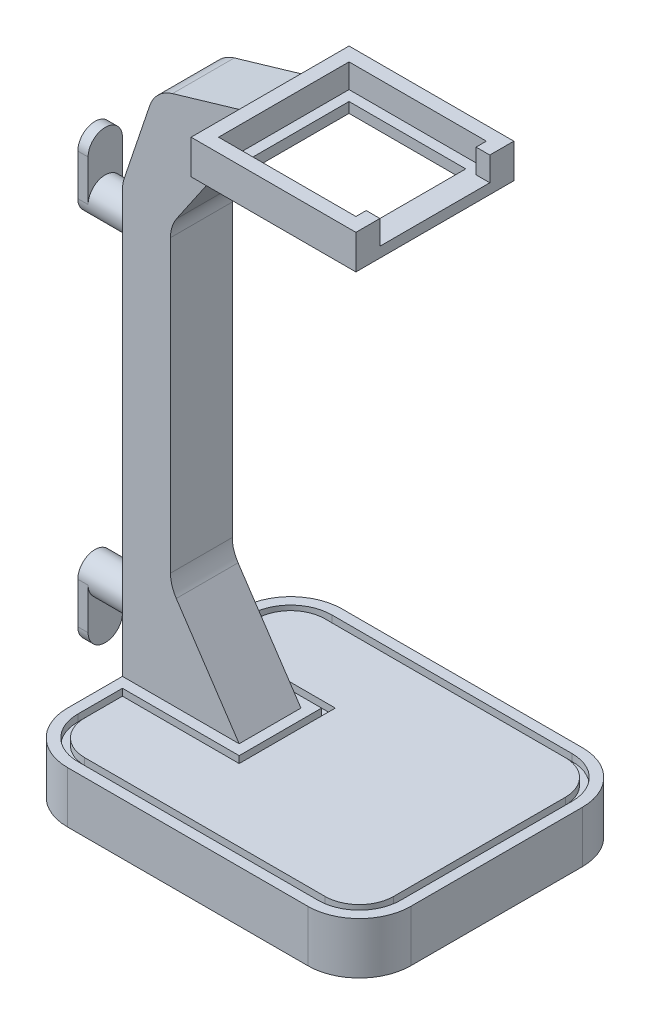
SolidWorks part; units mm, degrees
ref_plane "Front Plane" through (0, 0, 0) normal (0, 0, 1) x (1, 0, 0)
ref_plane "Top Plane" through (0, 0, 0) normal (0, 1, 0) x (1, 0, 0)
ref_plane "Right Plane" through (0, 0, 0) normal (1, 0, 0) x (0, 0, -1)
sketch "Sketch1" plane through (0, 0, 0) normal (0, 1, 0) x (1, 0, 0)
  line L1 (35, -40) -> (-35, -40)
  line L2 (50, -25) -> (50, 25)
  line L3 (35, 40) -> (-35, 40)
  line L4 (-50, -25) -> (-50, 25)
  line L5 (50, -40) -> (-50, 40) construction
  line L6 (50, 40) -> (-50, -40) construction
  arc A0 (50, 25) -> (35, 40) centre (35, 25) ccw
  arc A1 (50, -25) -> (35, -40) centre (35, -25) cw
  arc A2 (-50, -25) -> (-35, -40) centre (-35, -25) ccw
  arc A3 (-50, 25) -> (-35, 40) centre (-35, 25) cw
  point P0 (0, 0)
  dimension "D3" = 15
  dimension "D1" = 100
  dimension "D2" = 80
extrude "Boss-Extrude1" add sketch "Sketch1" along normal blind 15
sketch "Sketch3" plane through (0, 15, 0) normal (0, 1, 0) x (1, 0, 0)
  line L1 (-50, -9) -> (-36, -9)
  line L2 (-50, -9) -> (-50, 9)
  line L3 (-50, 9) -> (-36, 9)
  line L4 (-36, -9) -> (-36, 9)
  line L5 (-50, -9) -> (-36, 9) construction
  line L6 (-50, 9) -> (-36, -9) construction
  line L7 (-50, 25) -> (-50, -25) construction
  line L9 (-35, -40) -> (35, -40) construction
  point P0 (-43, 0)
  dimension "D1" = 14
  dimension "D2" = 18
  dimension "D3" = 40
extrude "Boss-Extrude2" add sketch "Sketch3" along normal blind 150 contours L3 L4 L1 L2
sketch "Sketch5" plane through (0, 0, 9) normal (0, 0, 1) x (1, 0, 0)
  line L0 (-36, 15) -> (-36, 45)
  line L1 (-36, 165) -> (-36, 15) construction
  line L2 (-36, 45) -> (-16, 15)
  line L3 (-35, 15) -> (35, 15) construction
  line L4 (-16, 15) -> (-36, 15)
  dimension "D1" = 30
  dimension "D2" = 20
extrude "Boss-Extrude3" add sketch "Sketch5" against normal blind 18 contours L2 L4 L0
ref_plane "Plane1" through (0, 175, 0) normal (0, 1, 0) x (1, 0, 0)
sketch "Sketch7" plane through (0, 175, 0) normal (0, 1, 0) x (1, 0, 0)
  line L0 (-36, -9) -> (-36, 9) construction
  line L1 (32, -23) -> (-16, -23)
  line L2 (32, -23) -> (32, 23)
  line L3 (32, 23) -> (-16, 23)
  line L4 (-16, -23) -> (-16, 23)
  line L5 (32, -23) -> (-16, 23) construction
  line L6 (32, 23) -> (-16, -23) construction
  line L7 (28, -19) -> (-12, -19)
  line L8 (28, -19) -> (28, 19)
  line L9 (28, 19) -> (-12, 19)
  line L10 (-12, -19) -> (-12, 19)
  line L11 (28, -19) -> (-12, 19) construction
  line L12 (28, 19) -> (-12, -19) construction
  line L13 (50, -25) -> (50, 25) construction
  point P0 (8, 0)
  point P6 (8, 0)
  dimension "D1" = 40
  dimension "D2" = 38
  dimension "D3" = 48
  dimension "D4" = 46
  dimension "D5" = 44
  dimension "D6" = 42
extrude "Boss-Extrude4" add sketch "Sketch7" against normal blind 10 separate body
sketch "Sketch8" plane through (0, 0, 9) normal (0, 0, 1) x (1, 0, 0)
  line L0 (-50, 165) -> (-16, 175)
  line L1 (-16, 175) -> (-16, 165)
  line L2 (-16, 165) -> (-36, 135.7425)
  line L3 (-36, 165) -> (-36, 45) construction
  line L4 (-50, 165) -> (-36, 165)
  line L5 (-36, 165) -> (-36, 135.7425)
extrude "Boss-Extrude5" add sketch "Sketch8" against normal blind 18 contours L0 L1 L2 L5 L4
sketch "Sketch9" plane through (-50, 0, 0) normal (-1, 0, 0) x (0, 0, 1)
  line L0 (-9, 15) -> (9, 15)
split line "Split Line3"
fillet "Fillet2" radius 10 2 edges at (-16, 165, 0) (-36, 135.7425, 0)
chamfer "Chamfer2" distance 10 angle 55 1 edges at (-50, 165, 0)
fillet "Fillet3" radius 10 2 edges at (-50, 139.3319, 0) (-40.4063, 167.8217, 0)
fillet "Fillet4" radius 10 1 edges at (-36, 45, 0)
sketch "Sketch11" plane through (0, 165, 0) normal (0, -1, 0) x (1, 0, 0)
  line L0 (28, 19) -> (28, -19) construction
  line L1 (-12, -19) -> (28, -19)
  line L2 (-12, -19) -> (-12, 19)
  line L3 (-12, 19) -> (28, 19)
  line L4 (28, -19) -> (28, 19)
  line L5 (-12, 19) -> (28, 19) construction
  line L6 (-9, -16) -> (25, -16)
  line L7 (25, -16) -> (25, 16)
  line L8 (-9, 16) -> (25, 16)
  line L9 (-9, -16) -> (-9, 16)
  dimension "D1" = 3
extrude "Boss-Extrude6" add sketch "Sketch11" against normal blind 3
sketch "Sketch12" plane through (32, 0, 0) normal (1, 0, 0) x (0, 0, -1)
  line L0 (-23, 175) -> (23, 175) construction
  line L1 (-16, 175) -> (16, 175)
  line L2 (-16, 175) -> (-16, 165)
  line L3 (-16, 165) -> (16, 165)
  line L4 (16, 175) -> (16, 165)
  line L5 (-23, 165) -> (23, 165) construction
  line L6 (-16, 168) -> (16, 168)
  point P8 (0, 165)
  line M6 (23, 175) -> (-23, 175)
  dimension "D1" = 3
  dimension "D2" = 32
extrude "Cut-Extrude2" cut sketch "Sketch12" against normal blind 5 contours L2 L6 L4 M6
sketch "Sketch13" plane through (0, 15, 0) normal (0, 1, 0) x (1, 0, 0)
  line L16 (-47, 12) -> (-13, 12)
  line L17 (-13, 12) -> (-13, -12)
  line L18 (-13, -12) -> (-47, -12)
  line L19 (-47, -12) -> (-47, -25)
  line L20 (-35, -37) -> (35, -37)
  line L21 (47, -25) -> (47, 25)
  line L22 (35, 37) -> (-35, 37)
  line L24 (-47, 12) -> (-13, 12)
  line L25 (-13, 12) -> (-13, -12)
  line L26 (-13, -12) -> (-47, -12)
  line L28 (-35, -37) -> (35, -37)
  line L29 (47, -25) -> (47, 25)
  line L30 (35, 37) -> (-35, 37)
  line L40 (-45, 14) -> (-11, 14)
  line L41 (-11, 14) -> (-11, -14)
  line L42 (-11, -14) -> (-45, -14)
  line L43 (-45, -14) -> (-45, -25)
  line L44 (-35, -35) -> (35, -35)
  line L45 (45, -25) -> (45, 25)
  line L46 (35, 35) -> (-35, 35)
  line L48 (-45, 14) -> (-11, 14)
  line L49 (-11, 14) -> (-11, -14)
  line L50 (-11, -14) -> (-45, -14)
  line L52 (-35, -35) -> (35, -35)
  line L53 (45, -25) -> (45, 25)
  line L54 (35, 35) -> (-35, 35)
  line L56 (-47, -12) -> (-47, -25)
  line L58 (-45, -14) -> (-45, -25)
  line L60 (-47, 25) -> (-47, 12)
  line L61 (-47, 25) -> (-47, 12)
  line L62 (-45, 25) -> (-45, 14)
  line L63 (-45, 25) -> (-45, 14)
  arc A8 (-47, -25) -> (-35, -37) centre (-35, -25) ccw
  arc A9 (35, -37) -> (47, -25) centre (35, -25) ccw
  arc A10 (47, 25) -> (35, 37) centre (35, 25) ccw
  arc A11 (-35, 37) -> (-47, 25) centre (-35, 25) ccw
  arc A12 (-47, -25) -> (-35, -37) centre (-35, -25) ccw
  arc A13 (35, -37) -> (47, -25) centre (35, -25) ccw
  arc A14 (47, 25) -> (35, 37) centre (35, 25) ccw
  arc A15 (-35, 37) -> (-47, 25) centre (-35, 25) ccw
  arc A20 (-45, -25) -> (-35, -35) centre (-35, -25) ccw
  arc A21 (35, -35) -> (45, -25) centre (35, -25) ccw
  arc A22 (45, 25) -> (35, 35) centre (35, 25) ccw
  arc A23 (-35, 35) -> (-45, 25) centre (-35, 25) ccw
  arc A24 (-45, -25) -> (-35, -35) centre (-35, -25) ccw
  arc A25 (35, -35) -> (45, -25) centre (35, -25) ccw
  arc A26 (45, 25) -> (35, 35) centre (35, 25) ccw
  arc A27 (-35, 35) -> (-45, 25) centre (-35, 25) ccw
  dimension "D1" = 3
  dimension "D2" = 5
extrude "Cut-Extrude3" cut sketch "Sketch13" against normal blind 2
sketch "Sketch15" plane through (-50, 0, 0) normal (-1, 0, 0) x (0, 0, 1)
  line L0 (-9, 15) -> (9, 15) construction
  circle A0 centre (0, 125) radius 5
  circle A1 centre (0, 29) radius 5
  dimension "D1" = 10
  dimension "D2" = 10
  dimension "D3" = 14
  dimension "D4" = 110
extrude "Boss-Extrude8" add sketch "Sketch15" along normal blind 14 contours A1 | A0
sketch "Sketch16" plane through (-64, 0, 0) normal (-1, 0, 0) x (0, 0, 1)
  line L0 (-5, 125) -> (-5, 137)
  line L1 (5, 125) -> (5, 137)
  line L2 (-5, 17) -> (-5, 29)
  line L3 (5, 17) -> (5, 29)
  arc A0 (-5, 125) -> (5, 125) centre (0, 125) ccw
  circle A1 centre (0, 125) radius 5 construction
  circle A2 centre (0, 125) radius 5 construction
  arc A4 (-5, 137) -> (5, 137) centre (0, 137) cw
  arc A5 (-5, 17) -> (5, 17) centre (0, 17) ccw
  arc A6 (-5, 29) -> (5, 29) centre (0, 29) cw
  circle A8 centre (0, 29) radius 5 construction
  point P18 (0, 0)
  dimension "D2" = 12
  dimension "D1" = 12
extrude "Boss-Extrude10" add sketch "Sketch16" along normal blind 3 contours L3 A6 L2 A5 | L1 A4 L0 A0
